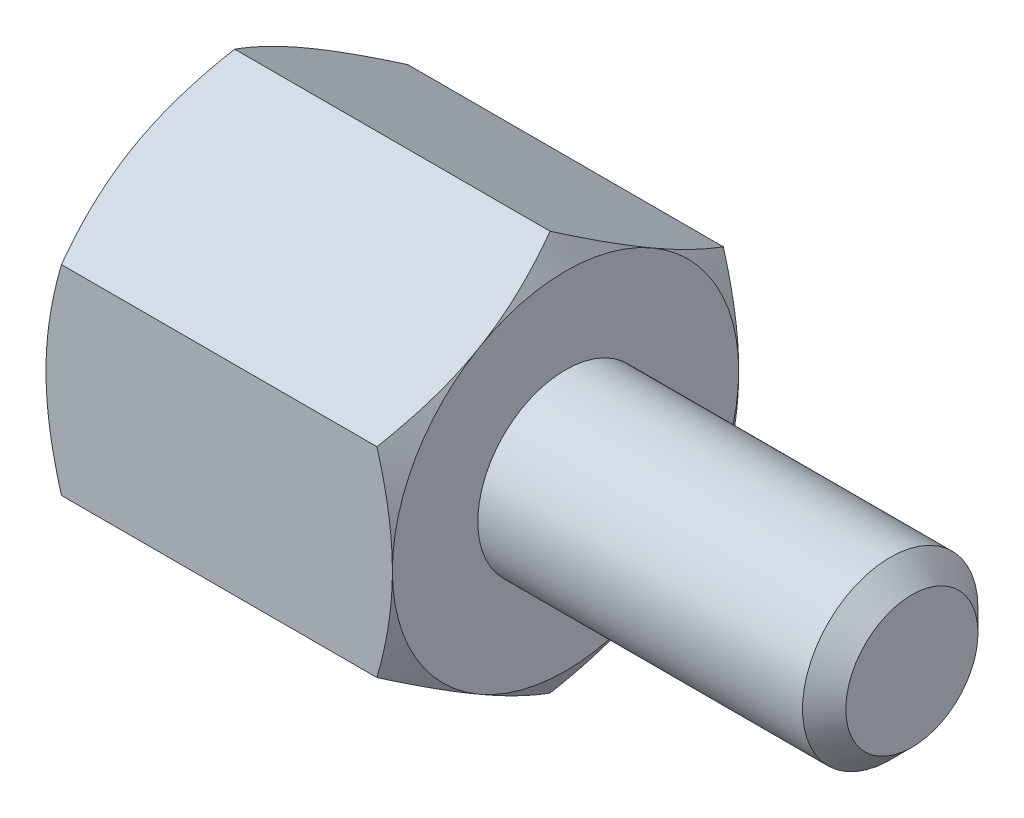
SolidWorks part; units mm, degrees
material "AISI 304"
ref_plane "Front Plane" through (0, 0, 0) normal (0, 0, 1) x (1, 0, 0)
ref_plane "Top Plane" through (0, 0, 0) normal (0, 1, 0) x (1, 0, 0)
ref_plane "Right Plane" through (0, 0, 0) normal (1, 0, 0) x (0, 0, -1)
sketch "Sketch1" plane through (0, 0, 0) normal (0, 0, 1) x (1, 0, 0)
  line L0 (-9.525, 0) -> (9.525, 0) construction
  line L1 (9.525, 2.413) -> (9.525, -2.413) construction
  line L2 (-9.525, 4.7625) -> (-9.525, -4.7625) construction
  line L3 (-4.7625, 2.413) -> (-4.7625, -2.413) construction
  line L4 (-4.7625, -2.413) -> (-9.525, -2.413) construction
  line L5 (-4.7625, 2.413) -> (-9.525, 2.413) construction
  line L6 (-9.525, 4.7625) -> (0, 4.7625) construction
  line L7 (-9.525, -4.7625) -> (0, -4.7625) construction
  point P2 (0, 0)
  point P8 (-4.7625, 0)
  point P13 (5.9531, -2.413)
  dimension "Hex" = 9.525
  dimension "Male Thread" = 4.826
  dimension "A" = 9.525
  dimension "B" = 9.525
  dimension "C" = 4.7625
  dimension "Female Thread" = 4.826
  dimension "D1" = 3.5719
ref_plane "Plane1" through (9.525, 0, 0) normal (1, 0, 0) x (0, 0, -1)
sketch "Sketch2" plane through (9.525, 0, 0) normal (1, 0, 0) x (0, 0, -1)
  circle A0 centre (0, 0) radius 2.413
extrude "Extrude1" add sketch "Sketch2" against normal up to vertex (9.525 mm away) up to point (0, 0, 0)
sketch "Sketch3" plane through (9.525, 0, 0) normal (1, 0, 0) x (0, 0, -1)
  circle A1 centre (0, 0) radius 2.413
  circle A2 centre (0, 0) radius 2.413
  dimension "D1" = 0
curve "Helix/Spiral1" [suppressed] pitch 0.7937 height 10.3188 turns 13 parameters "Male Pitch"=0.7937
chamfer "Chamfer1" distance 0.5953 angle 45 1 edges at (9.525, 0, -2.413)
sketch "Sketch4" plane through (0, 0, 0) normal (0, 0, 1) x (1, 0, 0)
  line L0 (9.525, 2.413) -> (10.2195, 2.413)
  line L1 (10.2195, 2.413) -> (9.9219, 1.8974)
  line L2 (9.9219, 1.8974) -> (9.8227, 1.8974)
  line L3 (9.8227, 1.8974) -> (9.525, 2.413)
  line L4 (9.8723, 1.8974) -> (9.8723, 2.413) construction
  line L5 (9.6738, 2.1552) -> (10.0707, 2.1552) construction
  dimension "D1" = 0.0992
  dimension "D2" = 0.3969
  dimension "D3" = 60
sweep "Cut-Sweep1" [suppressed] cut profiles "Sketch4" path "Helix/Spiral1"
sketch "Sketch16" [suppressed] plane through (0, 0, 0) normal (0, 0, 1) x (1, 0, 0)
  line L0 (0, 1.8949) -> (1.3891, 1.8949)
  line L1 (1.3891, 1.8949) -> (1.9072, 2.413)
  line L2 (1.9072, 2.413) -> (0, 2.413)
  line L3 (0, 2.413) -> (0, 1.8949)
  line L4 (9.525, 2.413) -> (10.2195, 2.413) construction
  line L5 (0, 0) -> (9.525, 0) construction
  line L6 (9.525, -1.8177) -> (9.525, 1.8177) construction
  dimension "D1" = 1.3891
  dimension "D2" = 45
  dimension "D3" = 0.0025
revolve "Cut-Revolve1" [suppressed] cut sketch "Sketch16" angle 360 about L5
ref_plane "Plane2" through (0, 0, 0) normal (1, 0, 0) x (0, 0, -1)
sketch "Sketch7" plane through (0, 0, 0) normal (1, 0, 0) x (0, 0, -1)
  line L1 (0, 5.4993) -> (-4.7625, 2.7496)
  line L2 (-4.7625, 2.7496) -> (-4.7625, -2.7496)
  line L3 (-4.7625, -2.7496) -> (0, -5.4993)
  line L4 (0, -5.4993) -> (4.7625, -2.7496)
  line L5 (4.7625, -2.7496) -> (4.7625, 2.7496)
  line L6 (4.7625, 2.7496) -> (0, 5.4993)
  circle A0 centre (0, 0) radius 4.7625 construction
extrude "Extrude4" add sketch "Sketch7" against normal up to vertex (9.525 mm away) up to point (-9.525, 0, 0)
sketch "Sketch17" plane through (0, 0, 0) normal (0, 0, 1) x (1, 0, 0)
  line L0 (-9.525, -5.4993) -> (0, -5.4993) construction
  line L1 (-9.525, 5.4993) -> (0, 5.4993) construction
  line L2 (-9.525, -5.4993) -> (0, -5.4993)
  line L3 (-9.525, 5.4993) -> (0, 5.4993)
sketch "Sketch8" plane through (-9.525, 0, 0) normal (-1, 0, 0) x (0, 0, 1)
  circle A0 centre (0, 0) radius 4.7625 construction
  circle A1 centre (0, 0) radius 4.7625
extrude "Extrude5" cut sketch "Sketch8" against normal through all draft 60 flip side to cut
sketch "Sketch9" plane through (0, 0, 0) normal (1, 0, 0) x (0, 0, -1)
  circle A0 centre (0, 0) radius 4.7625 construction
  circle A1 centre (0, 0) radius 4.7625
extrude "Extrude6" cut sketch "Sketch9" against normal through all draft 60 flip side to cut
sketch "Sketch10" plane through (-9.525, 0, 0) normal (-1, 0, 0) x (0, 0, 1)
  line L0 (0, 0) -> (-1.7062, 1.7062) construction
  line L1 (0, 0) -> (-2.413, 0) construction
  circle A0 centre (0, 0) radius 2.413
  dimension "D1" = 45
extrude "Extrude7" cut sketch "Sketch10" against normal up to vertex (4.7625 mm away) up to point (-4.7625, 0, 0)
sketch "Sketch11" plane through (-9.525, 0, 0) normal (-1, 0, 0) x (0, 0, 1)
  circle A0 centre (0, 0) radius 2.413 construction
  circle A1 centre (0, 0) radius 2.413
curve "Helix/Spiral2" pitch 0.7937 height 4.7625 turns 6 parameters "Female Pitch"=0.7937
sketch "Sketch12" plane through (0, 0, 0) normal (0, 0, 1) x (1, 0, 0)
  line L0 (-10.2195, 2.413) -> (-9.9219, 1.8974)
  line L1 (-9.9219, 1.8974) -> (-9.8227, 1.8974)
  line L2 (-9.8227, 1.8974) -> (-9.525, 2.413)
  line L3 (-10.2195, 2.413) -> (-9.525, 2.413)
  line L4 (-9.8723, 1.8974) -> (-9.8723, 2.413) construction
  line L5 (-9.525, 4.7625) -> (-9.525, -4.7625) construction
  line L6 (-10.0707, 2.1552) -> (-9.6738, 2.1552) construction
  dimension "D1" = 60
  dimension "D2" = 0.0992
  dimension "D3" = 0.3969
sweep "Sweep3" [suppressed] add profiles "Sketch12" path "Helix/Spiral2"
sketch "Sketch13" plane through (-9.525, 0, 0) normal (-1, 0, 0) x (0, 0, 1)
  circle A2 centre (0, 0) radius 2.4638
  circle A3 centre (0, 0) radius 2.4638
  dimension "D1" = 0.0508
extrude "Extrude8" [suppressed] cut sketch "Sketch13" along normal through all and the other way through all draft 45
equation "\"D3@Helix/Spiral1\" = \"B@Sketch1\"+\"Male Pitch@Helix/Spiral1\"*1"
equation "\"D1@Chamfer1\" = \"Male Pitch@Helix/Spiral1\"*.750"
equation "\"D1@Sketch4\" = \"Male Pitch@Helix/Spiral1\"*.125"
equation "\"D2@Sketch4\" = \"Male Pitch@Helix/Spiral1\"*.5"
equation "\"D2@Sketch12\" = \"Male Pitch@Helix/Spiral1\"*.125"
equation "\"D3@Sketch12\" = \"Male Pitch@Helix/Spiral1\"*.5"
equation "\"D3@Helix/Spiral2\" = \"C@Sketch1\""
equation "\"Female Thread@Sketch1\" = \"Male Thread@Sketch1\""
equation "\"Female Pitch@Helix/Spiral2\" = \"Male Pitch@Helix/Spiral1\""
equation "\"D1@Sketch16\" = \"Male Pitch@Helix/Spiral1\"*1.75"
equation "\"D1@Sketch1\" = \"Male Pitch@Helix/Spiral1\"*4.5"
